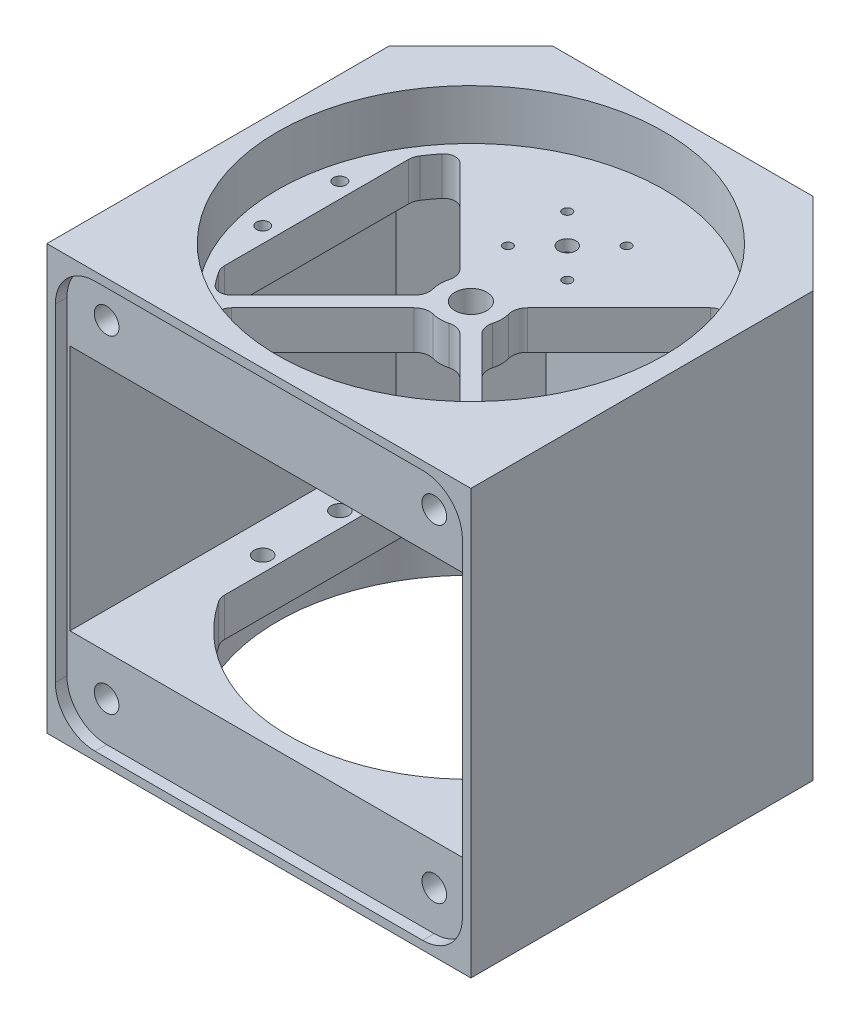
SolidWorks part; units mm, degrees
ref_plane "Front Plane" through (0, 0, 0) normal (0, 0, 1) x (1, 0, 0)
ref_plane "Top Plane" through (0, 0, 0) normal (0, 1, 0) x (1, 0, 0)
ref_plane "Right Plane" through (0, 0, 0) normal (1, 0, 0) x (0, 0, -1)
sketch "Sketch1" plane through (0, 0, 0) normal (0, 0, 1) x (1, 0, 0)
  line L5 (55, 55) -> (-55, 55)
  line L6 (55, 55) -> (55, -55)
  line L7 (55, -55) -> (-55, -55)
  line L12 (52.8, -42.5) -> (52.8, 42.5)
  line L13 (42.5, 52.8) -> (-42.5, 52.8)
  line L14 (-52.8, 42.5) -> (-52.8, -42.5)
  line L15 (-42.5, -52.8) -> (42.5, -52.8)
  line L16 (-55, 55) -> (-55, -55)
  line L17 (55, 55) -> (-55, -55) construction
  line L18 (55, -55) -> (-55, 55) construction
  arc A12 (52.8, 42.5) -> (42.5, 52.8) centre (42.5, 42.5) ccw
  arc A13 (-42.5, 52.8) -> (-52.8, 42.5) centre (-42.5, 42.5) ccw
  arc A14 (-52.8, -42.5) -> (-42.5, -52.8) centre (-42.5, -42.5) ccw
  arc A15 (42.5, -52.8) -> (52.8, -42.5) centre (42.5, -42.5) ccw
  point P0 (0, 0)
  dimension "D2" = 110
extrude "Boss-Extrude1" add sketch "Sketch1" against normal blind 3
sketch "Sketch2" plane through (0, -55, 0) normal (0, -1, 0) x (1, 0, 0)
  line L0 (55, -3) -> (55, -88.7868)
  line L1 (55, -88.7868) -> (33.7868, -110)
  line L2 (33.7868, -110) -> (-33.7868, -110)
  line L3 (-33.7868, -110) -> (-55, -88.7868)
  line L4 (-55, -88.7868) -> (-55, -3)
  line L5 (-55, -3) -> (55, -3) construction
  line L6 (-55, -3) -> (55, -3) construction
  line L7 (52, -3) -> (52, -87.5442)
  line L8 (-55, -3) -> (-55, 0) construction
  line L9 (-55, 0) -> (55, 0) construction
  line L10 (0, -110) -> (0, 0) construction
  line L11 (52, -87.5442) -> (32.5442, -107)
  line L12 (32.5442, -107) -> (-32.5442, -107)
  line L13 (-32.5442, -107) -> (-52, -87.5442)
  line L14 (-52, -87.5442) -> (-52, -3)
  line L15 (52, -3) -> (55, -3)
  line L16 (-55, -3) -> (-52, -3)
  circle A0 centre (0, -55) radius 50 construction
  dimension "D4" = 100
  dimension "D1" = 110
  dimension "D2" = 135
  dimension "D3" = 135
  dimension "D5" = 30
  dimension "D6" = 3
extrude "Boss-Extrude2" add sketch "Sketch2" against normal up to surface (110 mm away) up to face at (0, 55, -1.5)
sketch "Sketch3" plane through (0, -55, 0) normal (0, -1, 0) x (1, 0, 0)
  line L0 (-52, -3) -> (-52, -87.5442)
  line L1 (-52, -87.5442) -> (-32.5442, -107)
  line L2 (-32.5442, -107) -> (32.5442, -107)
  line L3 (32.5442, -107) -> (52, -87.5442)
  line L4 (52, -87.5442) -> (52, -3)
  line L5 (52, -3) -> (-52, -3)
  circle A0 centre (0, -55) radius 50.2
  dimension "D1" = 100.4
extrude "Boss-Extrude3" add sketch "Sketch3" against normal blind 3
sketch "Sketch4" plane through (0, -52, 0) normal (0, 1, 0) x (1, 0, 0)
  line L0 (11.2357, 3) -> (-11.2357, 3)
  circle A0 centre (0, 55) radius 50.2 construction
  circle A1 centre (0, 55) radius 50.2
  arc A2 (11.2357, 3) -> (-11.2357, 3) centre (0, 55) ccw
  circle A3 centre (0, 55) radius 53.2 construction
  dimension "D1" = 3
extrude "Boss-Extrude5" add sketch "Sketch4" along normal blind 10
sketch "Sketch5" plane through (0, -42, 0) normal (0, 1, 0) x (1, 0, 0)
  line L4 (52, 43.7643) -> (52, 66.2357)
  line L5 (11.2357, 107) -> (-11.2357, 107)
  line L6 (-52, 66.2357) -> (-52, 43.7643)
  line L7 (-11.2357, 3) -> (11.2357, 3)
  line L8 (52, 43.7643) -> (52, 66.2357)
  line L9 (11.2357, 107) -> (-11.2357, 107)
  line L10 (-52, 66.2357) -> (-52, 43.7643)
  line L11 (-11.2357, 3) -> (11.2357, 3)
  circle A0 centre (0, 55) radius 47.2
  circle A1 centre (0, 55) radius 50.2 construction
  arc A4 (11.2357, 3) -> (52, 43.7643) centre (0, 55) ccw
  arc A5 (52, 66.2357) -> (11.2357, 107) centre (0, 55) ccw
  arc A6 (-11.2357, 107) -> (-52, 66.2357) centre (0, 55) ccw
  arc A7 (-52, 43.7643) -> (-11.2357, 3) centre (0, 55) ccw
  arc A8 (11.2357, 3) -> (52, 43.7643) centre (0, 55) ccw
  arc A9 (52, 66.2357) -> (11.2357, 107) centre (0, 55) ccw
  arc A10 (-11.2357, 107) -> (-52, 66.2357) centre (0, 55) ccw
  arc A11 (-52, 43.7643) -> (-11.2357, 3) centre (0, 55) ccw
  dimension "D2" = 3
  dimension "D1" = 0
extrude "Boss-Extrude6" add sketch "Sketch5" along normal blind 2
sketch "Sketch11" plane through (0, -52, 0) normal (0, 1, 0) x (1, 0, 0)
  line L0 (-52, 43.7643) -> (-52, 3) construction
  line L1 (-52, 3) -> (-46.4799, 3) construction
  line L2 (-46.4799, 3) -> (-11.2357, 3) construction
  line L3 (-11.2357, 107) -> (-32.5442, 107) construction
  line L4 (-32.5442, 107) -> (-52, 87.5442) construction
  line L5 (-52, 87.5442) -> (-52, 66.2357) construction
  line L6 (52, 66.2357) -> (52, 87.5442) construction
  line L7 (52, 87.5442) -> (32.5442, 107) construction
  line L8 (32.5442, 107) -> (11.2357, 107) construction
  line L9 (11.2357, 3) -> (46.4799, 3) construction
  line L10 (46.4799, 3) -> (52, 3) construction
  line L11 (52, 3) -> (52, 43.7643) construction
  line L12 (-52, 43.7643) -> (-52, 3)
  line L13 (-52, 3) -> (-46.4799, 3)
  line L14 (-46.4799, 3) -> (-11.2357, 3)
  line L15 (-11.2357, 107) -> (-32.5442, 107)
  line L16 (-32.5442, 107) -> (-52, 87.5442)
  line L17 (-52, 87.5442) -> (-52, 66.2357)
  line L18 (52, 66.2357) -> (52, 87.5442)
  line L19 (52, 87.5442) -> (32.5442, 107)
  line L20 (32.5442, 107) -> (11.2357, 107)
  line L21 (11.2357, 3) -> (46.4799, 3)
  line L22 (46.4799, 3) -> (52, 3)
  line L23 (52, 3) -> (52, 43.7643)
  arc A0 (-52, 43.7643) -> (-11.2357, 3) centre (0, 55) ccw construction
  arc A1 (-11.2357, 107) -> (-52, 66.2357) centre (0, 55) ccw construction
  arc A2 (52, 66.2357) -> (11.2357, 107) centre (0, 55) ccw construction
  arc A3 (11.2357, 3) -> (52, 43.7643) centre (0, 55) ccw construction
  arc A4 (-52, 43.7643) -> (-11.2357, 3) centre (0, 55) ccw
  arc A5 (-11.2357, 107) -> (-52, 66.2357) centre (0, 55) ccw
  arc A6 (52, 66.2357) -> (11.2357, 107) centre (0, 55) ccw
  arc A7 (11.2357, 3) -> (52, 43.7643) centre (0, 55) ccw
extrude "Boss-Extrude14" add sketch "Sketch11" along normal blind 20
sketch "Sketch12" plane through (0, -40, 0) normal (0, 1, 0) x (1, 0, 0)
  line L4 (52, 43.7643) -> (52, 66.2357)
  line L5 (11.2357, 107) -> (-11.2357, 107)
  line L6 (-52, 66.2357) -> (-52, 43.7643)
  line L7 (-11.2357, 3) -> (11.2357, 3)
  line L8 (52, 43.7643) -> (52, 66.2357)
  line L9 (11.2357, 107) -> (-11.2357, 107)
  line L10 (-52, 66.2357) -> (-52, 43.7643)
  line L11 (-11.2357, 3) -> (11.2357, 3)
  circle A0 centre (0, 55) radius 47.2 construction
  circle A1 centre (0, 55) radius 47.2
  arc A4 (11.2357, 3) -> (52, 43.7643) centre (0, 55) ccw
  arc A5 (52, 66.2357) -> (11.2357, 107) centre (0, 55) ccw
  arc A6 (-11.2357, 107) -> (-52, 66.2357) centre (0, 55) ccw
  arc A7 (-52, 43.7643) -> (-11.2357, 3) centre (0, 55) ccw
  arc A8 (11.2357, 3) -> (52, 43.7643) centre (0, 55) ccw
  arc A9 (52, 66.2357) -> (11.2357, 107) centre (0, 55) ccw
  arc A10 (-11.2357, 107) -> (-52, 66.2357) centre (0, 55) ccw
  arc A11 (-52, 43.7643) -> (-11.2357, 3) centre (0, 55) ccw
  dimension "D1" = 0
extrude "Boss-Extrude16" add sketch "Sketch12" along normal up to surface (8 mm away) up to face at (38.445, -32, -93.445)
mirror "Mirror2" about plane through (0, 0, 0) normal (0, 1, 0) of "Boss-Extrude16", "Boss-Extrude14", "Boss-Extrude6", "Boss-Extrude5", "Boss-Extrude3"
sketch "Sketch13" plane through (0, 0, -3) normal (0, 0, 1) x (1, 0, 0)
  circle A0 centre (42.5, -42.5) radius 3.4195 construction
  circle A1 centre (-42.5, -42.5) radius 3.4195 construction
  circle A2 centre (-42.5, 42.5) radius 3.4195 construction
  circle A3 centre (42.5, 42.5) radius 3.4195 construction
  circle A4 centre (42.5, -42.5) radius 3.4195 construction
  circle A5 centre (-42.5, -42.5) radius 3.4195 construction
  circle A6 centre (-42.5, 42.5) radius 3.4195 construction
  circle A7 centre (42.5, 42.5) radius 3.4195 construction
  circle A8 centre (-42.5, 42.5) radius 3.2
  circle A9 centre (-42.5, -42.5) radius 3.2
  circle A10 centre (42.5, -42.5) radius 3.2
  circle A11 centre (42.5, 42.5) radius 3.2
  dimension "D1" = 6.4
extrude "Cut-Extrude2" cut sketch "Sketch13" against normal blind 15
sketch "Sketch14" plane through (0, 42, 0) normal (0, 1, 0) x (1, 0, 0)
  line L0 (0, 55) -> (0, -49945) construction
  line L1 (0, 55) -> (-35355.3391, 35410.3391) construction
  line L2 (0, 55) -> (35355.3391, 35410.3391) construction
  line L3 (-34.7597, 86.9313) -> (-6.8914, 59.063)
  line L4 (-31.9313, 89.7597) -> (-4.063, 61.8914)
  line L5 (-34.7597, 23.0687) -> (-6.8914, 50.937)
  line L6 (-4.063, 48.1086) -> (-31.9313, 20.2403)
  line L7 (6.8914, 50.937) -> (34.7597, 23.0687)
  line L8 (4.063, 48.1086) -> (31.9313, 20.2403)
  line L9 (4.063, 61.8914) -> (31.9313, 89.7597)
  line L10 (34.7597, 86.9313) -> (6.8914, 59.063)
  circle A0 centre (0, 55) radius 47.2 construction
  arc A1 (-34.7597, 23.0687) -> (-31.9313, 20.2403) centre (0, 55) ccw
  circle A2 centre (0, 55) radius 4.15
  arc A3 (-4.063, 48.1086) -> (4.063, 48.1086) centre (0, 55) ccw
  arc A4 (31.9313, 20.2403) -> (34.7597, 23.0687) centre (0, 55) ccw
  arc A5 (34.7597, 86.9313) -> (31.9313, 89.7597) centre (0, 55) ccw
  arc A6 (-31.9313, 89.7597) -> (-34.7597, 86.9313) centre (0, 55) ccw
  arc A7 (6.8914, 50.937) -> (6.8914, 59.063) centre (0, 55) ccw
  arc A8 (4.063, 61.8914) -> (-4.063, 61.8914) centre (0, 55) ccw
  arc A9 (-6.8914, 59.063) -> (-6.8914, 50.937) centre (0, 55) ccw
  dimension "D1" = 8.3
  dimension "D2" = 16
  dimension "D3" = 45
  dimension "D4" = 4
  dimension "D5" = 4
extrude "Boss-Extrude17" add sketch "Sketch14" against normal blind 10
fillet "Fillet1" radius 3 8 edges at (-34.7597, 37, -23.0687) (-31.9313, 37, -20.2403) (31.9313, 37, -20.2403) (34.7597, 37, -23.0687) (34.7597, 37, -86.9313) (31.9313, 37, -89.7597) (-31.9313, 37, -89.7597) (-34.7597, 37, -86.9313)
fillet "Fillet2" radius 4 8 edges at (4.063, 37, -61.8914) (-4.063, 37, -61.8914) (6.8914, 37, -59.063) (6.8914, 37, -50.937) (4.063, 37, -48.1086) (-4.063, 37, -48.1086) (-6.8914, 37, -50.937) (-6.8914, 37, -59.063)
sketch "Sketch15" plane through (0, 42, 0) normal (0, 1, 0) x (1, 0, 0)
  line L0 (-40, 80.0567) -> (-40, 29.9433)
  line L1 (0, -1000) -> (0, 49000) construction
  line L2 (40, 80.0567) -> (40, 29.9433)
  line L4 (44, 65) -> (-44, 65) construction
  line L5 (44, 65) -> (44, 45) construction
  line L6 (44, 45) -> (-44, 45) construction
  line L7 (-44, 65) -> (-44, 45) construction
  line L8 (44, 65) -> (-44, 45) construction
  line L9 (44, 45) -> (-44, 65) construction
  arc A0 (-36.9367, 84.3857) -> (-36.9367, 25.6143) centre (0, 55) ccw construction
  arc A1 (36.9367, 25.6143) -> (36.9367, 84.3857) centre (0, 55) ccw construction
  arc A2 (40, 29.9433) -> (40, 80.0567) centre (0, 55) ccw
  arc A3 (-40, 80.0567) -> (-40, 29.9433) centre (0, 55) ccw
  circle A4 centre (-44, 65) radius 1.65
  circle A5 centre (-44, 45) radius 1.65
  circle A6 centre (44, 45) radius 1.65
  circle A7 centre (44, 65) radius 1.65
  dimension "D4" = 3.3
  dimension "D1" = 80
  dimension "D2" = 88
  dimension "D3" = 20
extrude "Boss-Extrude18" add sketch "Sketch15" against normal blind 10
fillet "Fillet3" radius 4 4 edges at (-40, 37, -80.0567) (-40, 37, -29.9433) (40, 37, -29.9433) (40, 37, -80.0567)
mirror "Mirror8" about plane through (0, 0, 0) normal (0, 1, 0) of "Boss-Extrude17"
fillet "Fillet4" radius 3 8 edges at (34.7597, -37, -86.9313) (31.9313, -37, -89.7597) (-31.9313, -37, -89.7597) (-34.7597, -37, -86.9313) (-34.7597, -37, -23.0687) (-31.9313, -37, -20.2403) (31.9313, -37, -20.2403) (34.7597, -37, -23.0687)
fillet "Fillet5" radius 4 8 edges at (-4.063, -37, -61.8914) (4.063, -37, -61.8914) (-6.8914, -37, -59.063) (-6.8914, -37, -50.937) (-4.063, -37, -48.1086) (4.063, -37, -48.1086) (6.8914, -37, -50.937) (6.8914, -37, -59.063)
mirror "Mirror9" about plane through (0, 0, 0) normal (0, 1, 0) of "Boss-Extrude18"
fillet "Fillet6" radius 4 4 edges at (40, -37, -29.9433) (40, -37, -80.0567) (-40, -37, -80.0567) (-40, -37, -29.9433)
sketch "Sketch16" plane through (0, 42, 0) normal (0, 1, 0) x (1, 0, 0)
  line L0 (29.6393, 87.4677) -> (5.9343, 63.7627) construction
  line L1 (-5.9343, 63.7627) -> (-29.6393, 87.4677) construction
  line L2 (29.6393, 87.4677) -> (5.9343, 63.7627)
  line L3 (-5.9343, 63.7627) -> (-29.6393, 87.4677)
  arc A0 (29.6393, 87.4677) -> (29.3857, 91.9367) centre (27.518, 89.589) ccw construction
  arc A1 (2.0706, 62.7274) -> (5.9343, 63.7627) centre (3.1058, 66.5911) ccw construction
  arc A2 (2.0706, 62.7274) -> (-2.0706, 62.7274) centre (0, 55) ccw construction
  arc A3 (-5.9343, 63.7627) -> (-2.0706, 62.7274) centre (-3.1058, 66.5911) ccw construction
  arc A4 (-29.3857, 91.9367) -> (-29.6393, 87.4677) centre (-27.518, 89.589) ccw construction
  arc A5 (29.3857, 91.9367) -> (-29.3857, 91.9367) centre (0, 55) ccw construction
  arc A6 (29.6393, 87.4677) -> (29.3857, 91.9367) centre (27.518, 89.589) ccw
  arc A7 (2.0706, 62.7274) -> (5.9343, 63.7627) centre (3.1058, 66.5911) ccw
  arc A8 (2.0706, 62.7274) -> (-2.0706, 62.7274) centre (0, 55) ccw
  arc A9 (-5.9343, 63.7627) -> (-2.0706, 62.7274) centre (-3.1058, 66.5911) ccw
  arc A10 (-29.3857, 91.9367) -> (-29.6393, 87.4677) centre (-27.518, 89.589) ccw
  arc A11 (29.3857, 91.9367) -> (-29.3857, 91.9367) centre (0, 55) ccw
extrude "Boss-Extrude19" add sketch "Sketch16" against normal blind 5
sketch "Sketch17" plane through (0, 37, 0) normal (0, -1, 0) x (1, 0, 0)
  line L0 (0, -55) -> (0, -80) construction
  line L2 (7.7, -72.3) -> (-7.7, -72.3) construction
  line L3 (7.7, -72.3) -> (7.7, -87.7) construction
  line L4 (7.7, -87.7) -> (-7.7, -87.7) construction
  line L5 (-7.7, -72.3) -> (-7.7, -87.7) construction
  line L6 (7.7, -72.3) -> (-7.7, -87.7) construction
  line L7 (7.7, -87.7) -> (-7.7, -72.3) construction
  circle A0 centre (0, -80) radius 2.25
  circle A1 centre (7.7, -72.3) radius 1.2
  circle A2 centre (7.7, -87.7) radius 1.2
  circle A3 centre (-7.7, -87.7) radius 1.2
  circle A4 centre (-7.7, -72.3) radius 1.2
  dimension "D2" = 4.5
  dimension "D3" = 2.4
  dimension "D1" = 25
  dimension "D4" = 15.4
extrude "Cut-Extrude3" cut sketch "Sketch17" against normal through all
sketch "Sketch18" plane through (0, 37, 0) normal (0, -1, 0) x (1, 0, 0)
  circle A0 centre (0, -80) radius 8.2
  dimension "D1" = 16.4
extrude "Cut-Extrude4" cut sketch "Sketch18" against normal blind 2
sketch "Sketch20" plane through (0, -42, 0) normal (0, -1, 0) x (1, 0, 0)
  line L0 (40, -78.8797) -> (40, -31.1203) construction
  line L1 (-40, -31.1203) -> (-40, -78.8797) construction
  line L2 (40, -78.8797) -> (40, -31.1203)
  line L3 (-40, -31.1203) -> (-40, -78.8797)
  arc A0 (-36.9367, -84.3857) -> (36.9367, -84.3857) centre (0, -55) ccw
  arc A1 (-36.9367, -25.6143) -> (36.9367, -25.6143) centre (0, -55) cw
  arc A2 (36.9367, -84.3857) -> (39.3333, -81.0908) centre (0, -55) ccw construction
  arc A3 (39.3333, -81.0908) -> (40, -78.8797) centre (36, -78.8797) ccw construction
  arc A4 (40, -31.1203) -> (39.3333, -28.9092) centre (36, -31.1203) ccw construction
  arc A5 (39.3333, -28.9092) -> (36.9367, -25.6143) centre (0, -55) ccw construction
  arc A6 (-36.9367, -25.6143) -> (-39.3333, -28.9092) centre (0, -55) ccw construction
  arc A7 (-39.3333, -28.9092) -> (-40, -31.1203) centre (-36, -31.1203) ccw construction
  arc A8 (-40, -78.8797) -> (-39.3333, -81.0908) centre (-36, -78.8797) ccw construction
  arc A9 (-39.3333, -81.0908) -> (-36.9367, -84.3857) centre (0, -55) ccw construction
  arc A10 (36.9367, -84.3857) -> (39.3333, -81.0908) centre (0, -55) ccw
  arc A11 (39.3333, -81.0908) -> (40, -78.8797) centre (36, -78.8797) ccw
  arc A12 (40, -31.1203) -> (39.3333, -28.9092) centre (36, -31.1203) ccw
  arc A13 (39.3333, -28.9092) -> (36.9367, -25.6143) centre (0, -55) ccw
  arc A14 (-36.9367, -25.6143) -> (-39.3333, -28.9092) centre (0, -55) ccw
  arc A15 (-39.3333, -28.9092) -> (-40, -31.1203) centre (-36, -31.1203) ccw
  arc A16 (-40, -78.8797) -> (-39.3333, -81.0908) centre (-36, -78.8797) ccw
  arc A17 (-39.3333, -81.0908) -> (-36.9367, -84.3857) centre (0, -55) ccw
  arc A18 (-29.3857, -91.9367) -> (29.3857, -91.9367) centre (0, -55) ccw construction
  arc A19 (29.3857, -18.0633) -> (-29.3857, -18.0633) centre (0, -55) ccw construction
extrude "Cut-Extrude5" cut sketch "Sketch20" against normal up to surface (10 mm away) up to face at (-27.517, -32, -55)
sketch "Sketch23" plane through (0, -42, 0) normal (0, -1, 0) x (1, 0, 0)
  circle A0 centre (44, -65) radius 2.25
  circle A1 centre (44, -45) radius 2.25
  circle A2 centre (-44, -65) radius 2.25
  circle A3 centre (-44, -45) radius 2.25
  dimension "D1" = 4.5
extrude "Cut-Extrude6" cut sketch "Sketch23" against normal up to surface (10 mm away) up to face at (0, -32, -55)
equation "\"D5@Sketch14\"=\"D4@Sketch14\""
